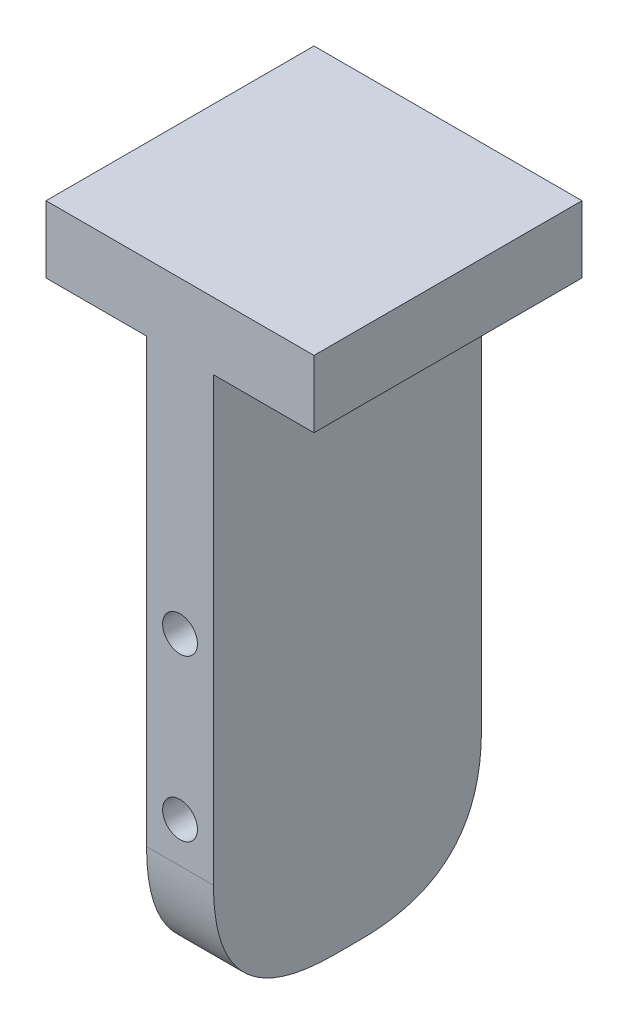
SolidWorks part; units mm, degrees
ref_plane "前基準面" through (0, 0, 0) normal (0, 0, 1) x (1, 0, 0)
ref_plane "上基準面" through (0, 0, 0) normal (0, 1, 0) x (1, 0, 0)
ref_plane "右基準面" through (0, 0, 0) normal (1, 0, 0) x (0, 0, -1)
sketch "草圖1" plane through (0, 0, 0) normal (0, 1, 0) x (1, 0, 0)
  line L1 (-10, -10) -> (10, -10)
  line L2 (-10, -10) -> (-10, 10)
  line L3 (-10, 10) -> (10, 10)
  line L4 (10, -10) -> (10, 10)
  line L5 (-10, -10) -> (10, 10) construction
  line L6 (-10, 10) -> (10, -10) construction
  point P0 (0, 0)
  dimension "D1" = 20
  dimension "D2" = 20
extrude "填料-伸長1" add sketch "草圖1" along normal blind 5
sketch "草圖2" plane through (0, 0, 0) normal (0, -1, 0) x (1, 0, 0)
  line L0 (-10, 10) -> (10, 10) construction
  line L1 (-2.5, -10) -> (2.5, -10)
  line L2 (-2.5, -10) -> (-2.5, 10)
  line L3 (-2.5, 10) -> (2.5, 10)
  line L4 (2.5, -10) -> (2.5, 10)
  line L5 (-2.5, -10) -> (2.5, 10) construction
  line L6 (-2.5, 10) -> (2.5, -10) construction
  point P0 (0, 0)
  dimension "D1" = 5
extrude "填料-伸長2" add sketch "草圖2" along normal blind 35
hole_wizard "Ø1.0mm 定位孔1" positions "草圖3" profile "草圖4" hole size "Ø1.0" standard "ISO"
sketch "草圖3" plane through (0, 0, 10) normal (0, 0, 1) x (1, 0, 0)
  line L0 (0, -35) -> (0, 5) construction
  line L1 (2.5, -35) -> (-2.5, -35) construction
  line L2 (-10, 5) -> (10, 5) construction
  point P0 (0, -18)
  point P2 (0, -30)
  dimension "D1" = 5
  dimension "D2" = 12
sketch "草圖4" plane through (0, -18, 10) normal (1, 0, 0) x (0, -1, 0)
  line L0 (0, 0) -> (0, 7.2811)
  line L1 (0, 7.2811) -> (1.3, 6.5)
  line L2 (1.3, 6.5) -> (1.3, 0)
  line L5 (1.3, 0) -> (0, 0)
  line L10 (0, 7.2811) -> (-1.3, 6.5) construction
  line L11 (0, -6.35) -> (0, 107.95) construction
  dimension "鑽孔直徑" = 2.6
  dimension "鑽孔深度" = 6.5
  dimension "導頭角度" = 118
mirror "鏡射1" about plane through (0, 0, 0) normal (0, 0, 1) of "Ø1.0mm 定位孔1"
sketch "草圖5" plane through (0, -35, 0) normal (0, -1, 0) x (1, 0, 0)
  line L0 (2.5, -10) -> (2.5, 10) construction
  line L1 (2.5, -10) -> (-2.5, -10)
  line L2 (2.5, -10) -> (2.5, 10)
  line L3 (2.5, 10) -> (-2.5, 10)
  line L4 (-2.5, -10) -> (-2.5, 10)
  line L5 (2.5, 0) -> (10, 0) construction
  line L6 (10, 10) -> (10, -10) construction
  line L7 (-2.5, 10) -> (-2.5, -10) construction
  dimension "D1" = 20
extrude "填料-伸長3" add sketch "草圖5" along normal blind 7
fillet "圓角1" radius 9 2 edges at (0, -42, 10) (0, -42, -10) conic rho 0.5
